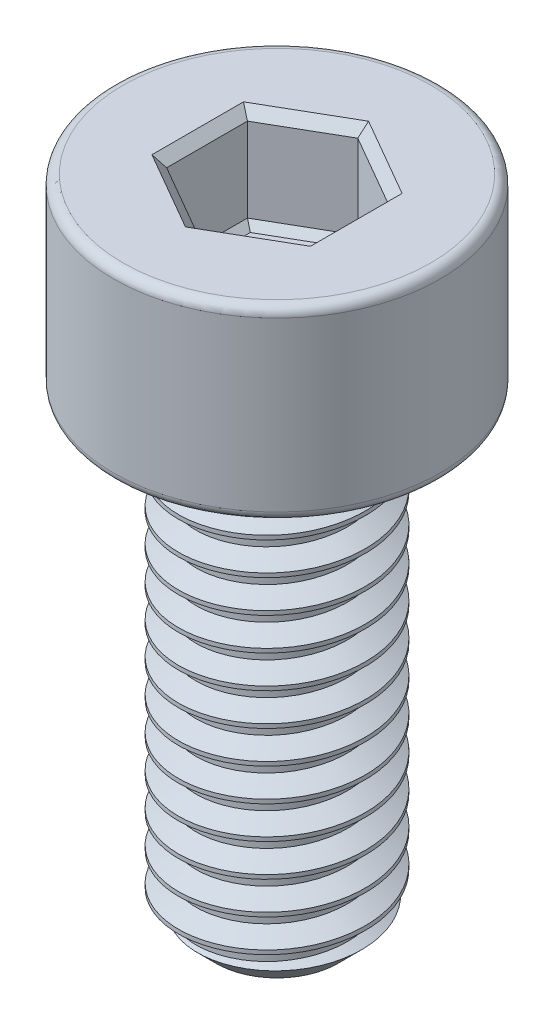
SolidWorks part; units mm, degrees
material "AISI Type A2 Tool Steel"
ref_plane "Front Plane" through (0, 0, 0) normal (0, 0, 1) x (1, 0, 0)
ref_plane "Top Plane" through (0, 0, 0) normal (0, 1, 0) x (1, 0, 0)
ref_plane "Right Plane" through (0, 0, 0) normal (1, 0, 0) x (0, 0, -1)
sketch "Sketch1" plane through (0, 0, 0) normal (0, 1, 0) x (1, 0, 0)
  circle A0 centre (0, 0) radius 2
  dimension "D1" = 4
extrude "Boss-Extrude1" add sketch "Sketch1" along normal blind 10
thread "Thread1" pitch 0.7 start angle 0, offset 1, length 0, pitch 0.7, diameter 4
ref_plane "Plane1" through (2, -1, 0) normal (0, 0, 1) x (1, 0, 0)
sketch "Thread Profile1" plane through (2, -1, 0) normal (0, 0, 1) x (1, 0, 0)
  line L0 (0, 0) -> (0, 0.7) construction
  line L11 (0, 0) -> (0, 0.6125)
  line L12 (0, 0.6125) -> (-0.3789, 0.3937)
  line L13 (-0.3789, 0.3937) -> (-0.3789, 0.2187)
  line L15 (-0.3789, 0.2187) -> (0, 0)
  line L17 (-0.3789, 0.3062) -> (0, 0.3062) construction
  point P2 (0, 0)
  dimension "Pitch" = 0.7
  dimension "Profile_Angle" = 60
  dimension "Profile_Land" = 0.175
  dimension "Profile_Height" = 0.3789
sketch "Sketch4" plane through (0, 10, 0) normal (0, -1, 0) x (-1, 0, 0)
  circle A0 centre (0, 0) radius 3.5
  dimension "D1" = 7
extrude "Boss-Extrude2" add sketch "Sketch4" against normal blind 4
fillet "Fillet1" radius 0.2 2 edges at (0, 10, -3.5) (0, 14, -3.5)
sketch "Sketch6" plane through (0, 0, 0) normal (0, 0, 1) x (1, 0, 0)
  line L0 (0, 0) -> (2.01, 0) construction
  line L1 (2.01, 0) -> (2.01, 0.7)
  line L2 (2.01, 0.7) -> (1.31, 0)
  line L3 (1.31, 0) -> (2.01, 0)
  line L4 (0, 0) -> (0, 0.3482) construction
  dimension "D1" = 0.7
  dimension "D2" = 45
  dimension "D3" = 2.01
revolve "Cut-Revolve1" cut sketch "Sketch6" angle 360 about L4
sketch "Sketch7" plane through (0, 14, 0) normal (0, 1, 0) x (1, 0, 0)
  line L1 (0, 1.7321) -> (-1.5, 0.866)
  line L2 (-1.5, 0.866) -> (-1.5, -0.866)
  line L3 (-1.5, -0.866) -> (0, -1.7321)
  line L4 (0, -1.7321) -> (1.5, -0.866)
  line L5 (1.5, -0.866) -> (1.5, 0.866)
  line L6 (1.5, 0.866) -> (0, 1.7321)
  circle A0 centre (0, 0) radius 1.5 construction
  dimension "D1" = 3
extrude "Cut-Extrude1" cut sketch "Sketch7" against normal blind 2
chamfer "Chamfer1" distance 0.2 angle 45 6 edges at (-1.5, 14, 0) (-0.75, 14, 1.299) (0.75, 14, 1.299) (1.5, 14, 0) (0.75, 14, -1.299) (-0.75, 14, -1.299)
sketch "Sketch8" plane through (0, 12, 0) normal (0, 1, 0) x (1, 0, 0)
  line L1 (0, 1.7321) -> (-1.5, 0.866)
  line L2 (-1.5, 0.866) -> (-1.5, -0.866)
  line L3 (-1.5, -0.866) -> (0, -1.7321)
  line L4 (0, -1.7321) -> (1.5, -0.866)
  line L5 (1.5, -0.866) -> (1.5, 0.866)
  line L6 (1.5, 0.866) -> (0, 1.7321)
  circle A0 centre (0, 0) radius 1.5 construction
extrude "Cut-Extrude2" cut sketch "Sketch8" against normal blind 0.15 draft 45
